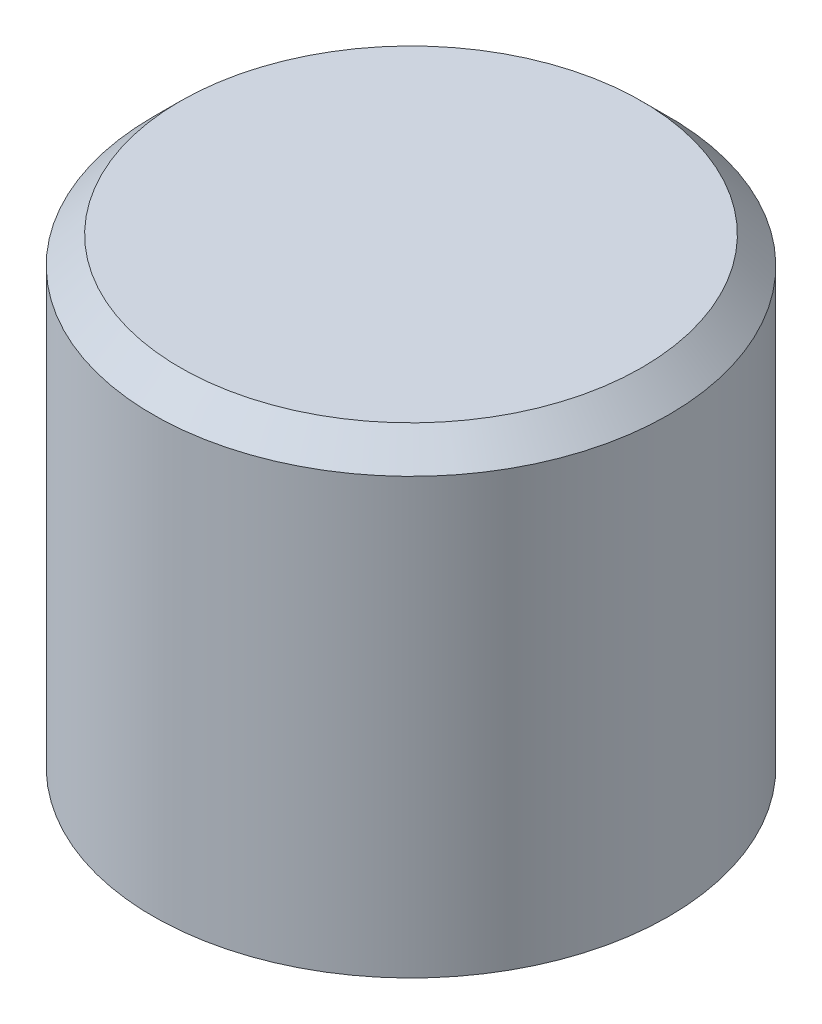
SolidWorks part; units mm, degrees
material "Brass"
ref_plane "Front Plane" through (0, 0, 0) normal (0, 0, 1) x (1, 0, 0)
ref_plane "Top Plane" through (0, 0, 0) normal (0, 1, 0) x (1, 0, 0)
ref_plane "Right Plane" through (0, 0, 0) normal (1, 0, 0) x (0, 0, -1)
sketch "Sketch1" plane through (0, 0, 0) normal (0, 0, 1) x (1, 0, 0)
  line L0 (0, 8.5) -> (0, -8.5) construction
  line L1 (0, 8.5) -> (8.5, 8.5)
  line L2 (9.5, 7.5) -> (9.5, -8.5)
  line L3 (9.5, -8.5) -> (8.5, -8.5)
  line L4 (8.5, -8.5) -> (8.5, -3.5)
  line L7 (5.5, -0.5) -> (0, -0.5)
  line L8 (0, -0.5) -> (0, 8.5)
  line L12 (8.5, -3.5) -> (5.5, -0.5)
  line L13 (8.5, 8.5) -> (9.5, 7.5)
  point P3 (0, 0)
  point P8 (7.5, 6.5)
  point P9 (4, 6.5)
  point P10 (4, -0.5)
  point P14 (8.5, -0.5)
  point P17 (9.5, 8.5)
  dimension "D1" = 17
  dimension "D2" = 9.5
  dimension "D3" = 1
  dimension "D4" = 9
revolve "Revolve1" add sketch "Sketch1" angle 360 about L0
sketch "Sketch2" plane through (0, -0.5, 0) normal (0, -1, 0) x (1, 0, 0)
  circle A1 centre (0, 0) radius 3.175
  dimension "D1" = 6.35
extrude "Cut-Extrude1" cut sketch "Sketch2" against normal offset from surface (7 mm away) 2 up to face at (-8.5, 8.5, 0)
sketch "Sketch3" plane through (0, 0, 0) normal (0, 0, 1) x (1, 0, 0)
  line L1 (8.5, 8.5) -> (-8.5, 8.5) construction
  circle A0 centre (0, 2.5) radius 1.1303
  dimension "D1" = 2.2606
  dimension "D2" = 6
extrude "Cut-Extrude2" cut sketch "Sketch3" against normal up to surface (9.4325 mm away) up to face at (-9.5, 7.5, 0)
